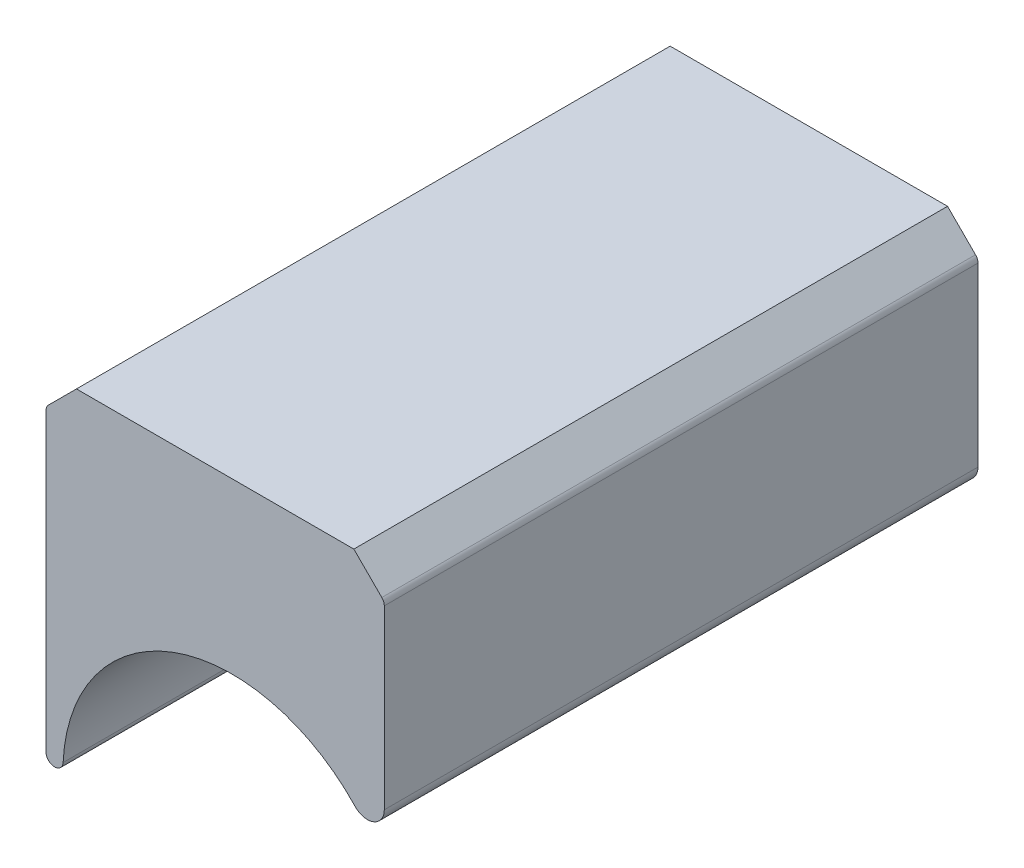
SolidWorks part; units mm, degrees
ref_plane "Front Plane" through (0, 0, 0) normal (0, 0, 1) x (1, 0, 0)
ref_plane "Top Plane" through (0, 0, 0) normal (0, 1, 0) x (1, 0, 0)
ref_plane "Right Plane" through (0, 0, 0) normal (1, 0, 0) x (0, 0, -1)
sketch "Sketch1" plane through (0, 0, 0) normal (0, 0, 1) x (1, 0, 0)
  line L0 (11, 20) -> (11, 10) construction
  line L1 (0, 0) -> (1, 0)
  line L2 (0, 0) -> (0, 20)
  line L3 (0, 20) -> (20, 20)
  line L4 (20, 4.3589) -> (20, 20)
  arc A0 (20, 4.3589) -> (1, 0) centre (11, 0) ccw
  point P8 (-16.6801, 4.8864)
  point P9 (-20.1722, 7.5133)
extrude "Boss-Extrude2" add sketch "Sketch1" along normal blind 35.1
sketch "Sketch2" plane through (0, 0, 0) normal (-1, 0, 0) x (0, 0, 1)
  line L0 (0, 0) -> (0, 6)
  line L1 (0, 20) -> (0, 0) construction
  line L2 (0, 6) -> (6, 6)
  line L3 (0, 0) -> (17, 0)
  line L4 (35.1, 0) -> (0, 0) construction
  line L5 (6, 6) -> (17, 0)
extrude "Cut-Extrude2" cut sketch "Sketch2" against normal blind 23.1
chamfer "Chamfer1" distance 1.8 angle 45 2 edges at (20, 20, 17.55) (0, 20, 17.55)
fillet "Fillet1" radius 20 2 edges at (0.5, 0, 17) (1.5, 6, 6)
fillet "Fillet2" radius 0.5 12 edges at (0, 18.2, 17.55) (20, 18.2, 17.55) (3, 6, 0.4501) (2.8157, 5.7461, 4.077) (1.4622, 3.0051, 11.4906) (1.0631, 1.1219, 15.4955) (1, 0, 28.5999) (0, 0, 28.5999) (0, 0.6201, 17.1581) (0, 3, 11.5) (0, 5.3799, 5.8419) (0, 6, 0.4501)
fillet "Fillet3" radius 1 1 edges at (20, 4.3589, 22.0543)
sketch "Hole Positions" plane through (0, 0, 35.1) normal (0, 0, 1) x (1, 0, 0)
  line L0 (5, 15.5) -> (11, 15.5) construction
  line L1 (11, 15.5) -> (15, 15.5) construction
  line L2 (11, 15.5) -> (11, 0) construction
  line L3 (5, 15.5) -> (5, 13.5) construction
  point P2 (0, 0)
  dimension "D1" = 6
  dimension "D2" = 4
  dimension "D3" = 2
  dimension "D4" = 15.5
